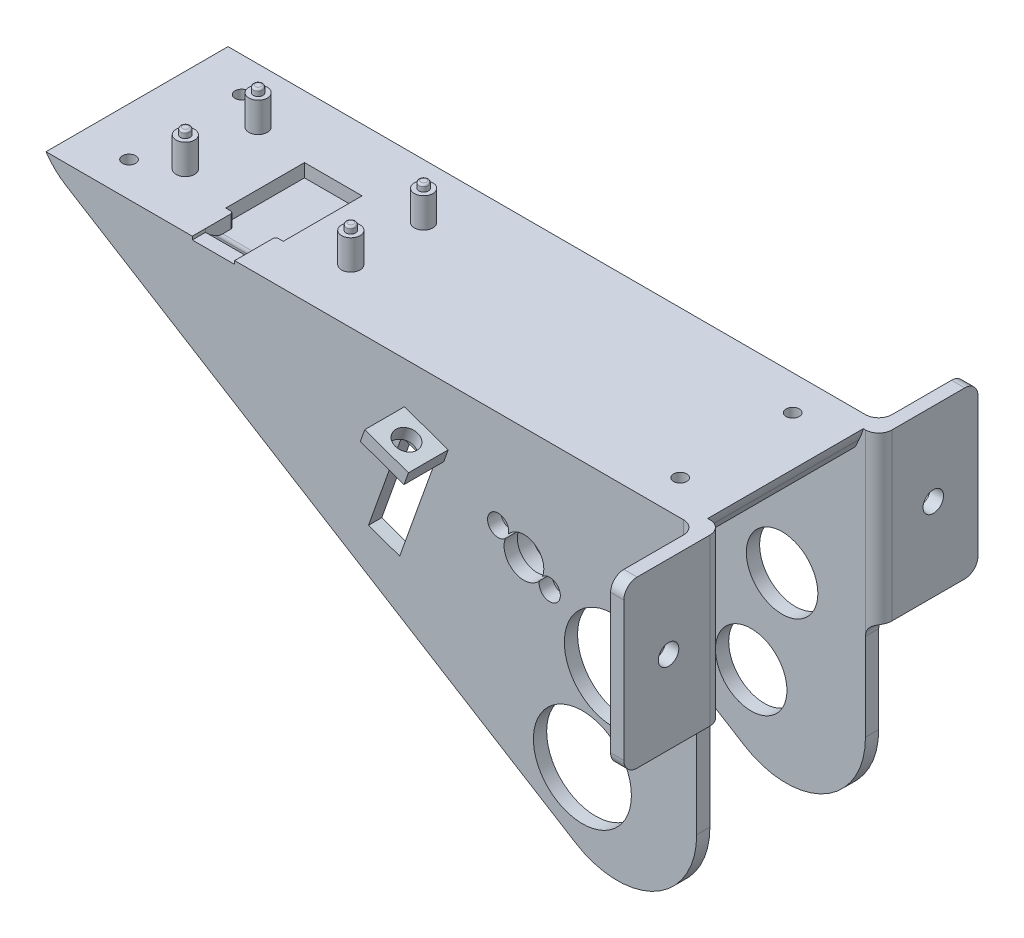
SolidWorks part; units mm, degrees
material "尼龙 101"
ref_plane "前视基准面" through (0, 0, 0) normal (0, 0, 1) x (1, 0, 0)
ref_plane "上视基准面" through (0, 0, 0) normal (0, 1, 0) x (1, 0, 0)
ref_plane "右视基准面" through (0, 0, 0) normal (1, 0, 0) x (0, 0, -1)
other "Configuration Table"
sketch "草图1" plane through (0, 0, 0) normal (0, 1, 0) x (1, 0, 0)
  line L1 (-50, 12.75) -> (50, 12.75)
  line L2 (-50, 12.75) -> (-50, -12.75)
  line L3 (-50, -12.75) -> (50, -12.75)
  line L4 (50, 12.75) -> (50, -12.75)
  line L5 (-50, 12.75) -> (50, -12.75) construction
  line L6 (-50, -12.75) -> (50, 12.75) construction
  point P0 (0, 0)
  dimension "D1" = 100
  dimension "D2" = 25.5
extrude "凸台-拉伸1" add sketch "草图1" along normal blind 3
sketch "草图2" plane through (0, 3, 0) normal (0, 1, 0) x (1, 0, 0)
  line L0 (0, 0) -> (0, 5.35) construction
  line L1 (-5.35, 5.35) -> (5.35, 5.35)
  line L2 (5.35, 5.35) -> (5.35, -7.55)
  line L3 (5.35, -7.55) -> (4.35, -7.55)
  line L4 (4.35, -7.55) -> (4.35, 4.35)
  line L5 (4.35, 4.35) -> (-4.35, 4.35)
  line L6 (-4.35, -7.55) -> (-4.35, 4.35)
  line L7 (-5.35, -7.55) -> (-4.35, -7.55)
  line L8 (-5.35, 5.35) -> (-5.35, -7.55)
  point P9 (0, 4.35)
  dimension "D1" = 8.7
  dimension "D2" = 11.9
  dimension "D3" = 4.35
  dimension "D4" = 1
  dimension "D5" = 1
extrude "凸台-拉伸2" add sketch "草图2" along normal blind 1.5
sketch "草图5" plane through (0, 3, 0) normal (0, 1, 0) x (1, 0, 0)
  circle A0 centre (-10.5, 5.5) radius 1.4
  circle A1 centre (-10.5, -5.5) radius 1.4
  circle A2 centre (-35.5, -5.5) radius 1.4
  circle A3 centre (-35.5, 5.5) radius 1.4
  dimension "D1" = 2.8
  dimension "D2" = 25
  dimension "D3" = 11
extrude "凸台-拉伸3" add sketch "草图5" along normal blind 4.5
sketch "草图6" plane through (0, 7.5, 0) normal (0, 1, 0) x (1, 0, 0)
  circle A0 centre (-35.5, -5.5) radius 0.725
  circle A1 centre (-35.5, 5.5) radius 0.725
  circle A2 centre (-10.5, 5.5) radius 0.725
  circle A3 centre (-10.5, -5.5) radius 0.725
  dimension "D1" = 1.45
extrude "凸台-拉伸4" add sketch "草图6" along normal blind 1
sketch "草图7" plane through (0, 3, 0) normal (0, 1, 0) x (1, 0, 0)
  line L0 (0, 0) -> (0, 12.75) construction
  line L1 (50, 12.75) -> (-50, 12.75) construction
  line L2 (0, 0) -> (50, 0) construction
  line L3 (50, -12.75) -> (50, 12.75) construction
  circle A0 centre (42.25, 8.5) radius 1
  circle A1 centre (-41, 8.5) radius 1
  circle A2 centre (-41, -8.5) radius 1
  circle A3 centre (42.25, -8.5) radius 1
  dimension "D1" = 83.25
extrude "切除-拉伸1" cut sketch "草图7" against normal blind 10
sketch "草图8" plane through (0, 0, 0) normal (0, -1, 0) x (1, 0, 0)
  circle A0 centre (-41, 8.5) radius 2
  circle A1 centre (42.25, 8.5) radius 2
  circle A2 centre (42.25, -8.5) radius 2
  circle A3 centre (-41, -8.5) radius 2
  dimension "D1" = 4
extrude "切除-拉伸2" cut sketch "草图8" against normal blind 1
fillet "圆角1" radius 2 4 edges at (-50, 1.5, -12.75) (50, 1.5, -12.75) (-50, 1.5, 12.75) (50, 1.5, 12.75)
fillet "圆角2" radius 0.3 4 edges at (-10.5, 8.5, -4.775) (-10.5, 8.5, 6.225) (-35.5, 8.5, 6.225) (-35.5, 8.5, -4.775)
sketch "草图15" plane through (0, 3, 0) normal (0, 1, 0) x (1, 0, 0)
  line L0 (-23, 0) -> (-23, 12.75) construction
  line L2 (-27.35, 4.35) -> (-18.65, 4.35)
  line L3 (-18.65, 4.35) -> (-18.65, -7.55)
  line L4 (-18.65, -7.55) -> (-19.8, -7.55)
  line L5 (-19.8, -7.55) -> (-19.8, -12.75)
  line L7 (-19.8, -12.75) -> (-26.2, -12.75)
  line L8 (-26.2, -7.55) -> (-26.2, -12.75)
  line L9 (-27.35, -7.55) -> (-26.2, -7.55)
  line L10 (-27.35, 4.35) -> (-27.35, -7.55)
  line L12 (42.25, 8.5) -> (-23, 8.5) construction
  point P14 (-23, -12.75)
  point P17 (-23, 4.35)
  dimension "D1" = 6.4
extrude "切除-拉伸8" cut sketch "草图15" against normal blind 2
sketch "草图17" plane through (0, 4.5, 0) normal (0, 1, 0) x (1, 0, 0)
  line L8 (-4.35, -7.55) -> (-4.35, 4.35)
  line L9 (-4.35, 4.35) -> (4.35, 4.35)
  line L10 (4.35, 4.35) -> (4.35, -7.55)
  line L11 (4.35, -7.55) -> (5.35, -7.55)
  line L12 (5.35, -7.55) -> (5.35, 5.35)
  line L13 (5.35, 5.35) -> (-5.35, 5.35)
  line L14 (-5.35, 5.35) -> (-5.35, -7.55)
  line L15 (-5.35, -7.55) -> (-4.35, -7.55)
  line L16 (-4.35, -7.55) -> (-4.35, 4.35)
  line L17 (-4.35, 4.35) -> (4.35, 4.35)
  line L18 (4.35, 4.35) -> (4.35, -7.55)
  line L19 (4.35, -7.55) -> (5.35, -7.55)
  line L20 (5.35, -7.55) -> (5.35, 5.35)
  line L21 (5.35, 5.35) -> (-5.35, 5.35)
  line L22 (-5.35, 5.35) -> (-5.35, -7.55)
  line L23 (-5.35, -7.55) -> (-4.35, -7.55)
  dimension "D1" = 0
extrude "切除-拉伸9" cut sketch "草图17" against normal blind 1.5
sketch "草图18" plane through (-19.8, 0, 0) normal (-1, 0, 0) x (0, 0, 1)
  line L0 (12.75, 1) -> (9.75, 1)
  line L2 (12.75, 1) -> (12.75, 3) construction
  line L3 (12.75, 2.6) -> (12.75, 1)
  line L5 (12.75, 3) -> (12.75, 0) construction
  line L6 (12.75, 2.6) -> (12.25, 2.6)
  line L7 (12.25, 2.6) -> (9.75, 1)
  line L8 (12.75, 3) -> (10.75, 3) construction
  dimension "D1" = 3
  dimension "D2" = 0.4
  dimension "D3" = 0.5
extrude "凸台-拉伸6" add sketch "草图18" along normal up to surface (6.4 mm away) up to face at (-26.2, 2, 10.15)
fillet "圆角3" radius 2 1 edges at (-23, 1, 9.75)
fillet "圆角5" radius 1 1 edges at (-23, 2.6, 12.25)
fillet "圆角6" radius 0.4 2 edges at (-19.8, 2, 7.55) (-26.2, 2, 7.55)
ref_plane "基准面1" through (0, 0, 0) normal (0, 0, -1) x (-1, 0, 0)
sketch "草图26" plane through (0, 0, -12.75) normal (0, 0, -1) x (-1, 0, 0)
  line L0 (50, 3) -> (-47.2265, -57.0098)
  line L1 (-50, 3) -> (-50, -58.7217)
  line L3 (-47.2265, -57.0098) -> (-50, -58.7217)
  line L4 (-50, 3) -> (50, 3)
  line L6 (-51, 3) -> (49.4801, 3) construction
  line L7 (-48, 3) -> (-50, 3) construction
extrude "凸台-拉伸12" add sketch "草图26" against normal mid plane 2
ref_plane "基准面2" through (0, 0, -11.75) normal (0, 0, -1) x (-1, 0, 0)
ref_plane "基准面3" through (0, 0, 0) normal (0, 0, 1) x (1, 0, 0)
mirror "镜向1" about plane through (0, 0, 0) normal (0, 0, 1) of "凸台-拉伸12"
sketch "草图34" plane through (0, 0, -13.75) normal (0, 0, -1) x (-1, 0, 0)
  line L0 (50, 15.0087) -> (50, 8.5792)
  line L1 (50, 8.5792) -> (50, 13) construction
  line L2 (45.2523, 0.0696) -> (38.3449, -4.1938)
  line L3 (-50, -58.7217) -> (50, 3) construction
  line L4 (50, 15.0087) -> (52.8395, -4.7654)
  line L5 (52.8395, -4.7654) -> (38.3449, -4.1938)
  arc A0 (45.2523, 0.0696) -> (50, 8.5792) centre (40, 8.5792) ccw
  point P12 (50, 3)
  dimension "D1" = 10
extrude "切除-拉伸20" cut sketch "草图34" against normal up to surface (27.5 mm away) up to face at (16.6667, -17.5739, 13.75)
sketch "草图35" plane through (0, 0, -11.75) normal (0, 0, 1) x (1, 0, 0)
  line L9 (50, 10.631) -> (50, 5.5397)
  line L10 (57.0725, -23.7563) -> (50, 10.631)
  line L11 (33.7407, -30.9984) -> (57.0725, -23.7563)
  line L12 (49.0355, 1.255) -> (33.7407, -30.9984)
  arc A2 (49.0355, 1.255) -> (50, 5.5397) centre (40, 5.5397) ccw
extrude "切除-拉伸21" cut sketch "草图35" along normal up to surface (23.5 mm away) up to face at (30.8649, -10.5443, 11.75)
sketch "草图37" plane through (0, 0, -13.75) normal (0, 0, -1) x (-1, 0, 0)
  line L0 (-50, -58.7217) -> (-31.6973, -47.425)
  line L1 (-50, 3) -> (-50, -58.7217) construction
  line L2 (-50, -58.7217) -> (-50, -37.2134)
  line L3 (-50, -58.7217) -> (45.2523, 0.0696) construction
  arc A0 (-50, -37.2134) -> (-31.6973, -47.425) centre (-38, -37.2134) ccw
  dimension "D1" = 12
  dimension "D2" = 12
extrude "切除-拉伸22" cut sketch "草图37" against normal blind 30
sketch "草图41" plane through (0, 0, 13.75) normal (0, 0, 1) x (1, 0, 0)
  circle A0 centre (23.9052, -13.9776) radius 3
extrude "切除-拉伸25" cut sketch "草图41" against normal blind 50
sketch "草图48" plane through (0, 0, 13.75) normal (0, 0, 1) x (1, 0, 0)
  line L4 (-19.8024, 3) -> (-26.1988, 3)
  line L6 (-19.8024, 2.5) -> (-26.1988, 2.5)
  line L8 (-26.1988, 3) -> (-26.1988, 2.5)
  line L9 (-19.8024, 2.5) -> (-19.8024, 3)
extrude "切除-拉伸30" cut sketch "草图48" against normal blind 5
sketch "草图50" plane through (50, 0, 0) normal (1, 0, 0) x (0, 0, -1)
  line L0 (0, 0) -> (0, -12.9975) construction
  line L1 (11.75, 3) -> (26.75, 3)
  line L2 (11.75, 3) -> (11.75, -22)
  line L3 (11.75, -22) -> (26.75, -22)
  line L4 (26.75, 3) -> (26.75, -22)
  line L5 (-26.75, 3) -> (-26.75, -22)
  line L6 (-11.75, -22) -> (-26.75, -22)
  line L7 (-11.75, 3) -> (-11.75, -22)
  line L8 (-11.75, 3) -> (-26.75, 3)
  circle A0 centre (-20, -9.5) radius 1.55
  circle A1 centre (20, -9.5) radius 1.55
  point P8 (20, -9.5)
  point P14 (-20, -9.5)
  dimension "D1" = 12.5
  dimension "D2" = 40
extrude "凸台-拉伸14" add sketch "草图50" along normal blind 2
fillet "圆角8" radius 2 6 edges at (51, 3, -26.75) (51, -22, -26.75) (51, -22, 26.75) (51, 3, 26.75) (50, -9.5, 13.75) (50, -9.5, -13.75)
fillet "圆角9" radius 2 2 edges at (50, -22, 12.75) (50, -22, -12.75)
fillet "圆角10" radius 2 2 edges at (52, -9.5, -11.75) (52, -9.5, 11.75)
sketch "草图51" plane through (0, 0, 13.75) normal (0, 0, 1) x (1, 0, 0)
  line L0 (23.9052, -13.9776) -> (17.8526, -10.4832) construction
  line L1 (23.9052, -13.9776) -> (19.6123, -21.4131) construction
  circle A0 centre (20.008, -11.7276) radius 0.8
  circle A1 centre (27.8023, -16.2276) radius 0.8
  dimension "D1" = 9
  dimension "D2" = 1.6
sketch "草图52" plane through (0, 0, 11.75) normal (0, 0, -1) x (-1, 0, 0)
  line L1 (-21.026, -5.9645) -> (-32.2843, -12.4645)
  line L2 (-21.026, -5.9645) -> (-15.526, -15.4908)
  line L3 (-15.526, -15.4908) -> (-26.7843, -21.9908)
  line L4 (-32.2843, -12.4645) -> (-26.7843, -21.9908)
  line L5 (-21.026, -5.9645) -> (-26.7843, -21.9908) construction
  line L6 (-15.526, -15.4908) -> (-32.2843, -12.4645) construction
  circle A0 centre (-23.9052, -13.9776) radius 3.5
  point P0 (-23.9052, -13.9776)
  dimension "D1" = 13
  dimension "D2" = 11
extrude "凸台-拉伸15" add sketch "草图52" along normal blind 2.5
extrude "切除-拉伸31" cut sketch "草图51" against normal up to surface (4.5 mm away) up to face at (23.9052, -13.9776, 9.25)
sketch "草图53" plane through (0, 0, 13.75) normal (0, 0, 1) x (1, 0, 0)
  line L0 (23.9052, -13.9776) -> (25.4052, -13.9776) construction
  circle A0 centre (20.008, -11.7276) radius 1.6
  circle A2 centre (27.8023, -16.2276) radius 1.6
  point P8 (27.8023, -16.2276)
extrude "切除-拉伸34" cut sketch "草图53" against normal blind 2
fillet "圆角11" radius 1 4 edges at (29.5343, -17.2276, 11.75) (21.1552, -18.7408, 11.75) (18.276, -10.7276, 11.75) (26.6552, -9.2145, 11.75)
sketch "草图54" plane through (0, 0, -13.75) normal (0, 0, -1) x (-1, 0, 0)
  circle A0 centre (-23.9052, -13.9776) radius 6.5
extrude "切除-拉伸35" cut sketch "草图54" against normal up to surface (2 mm away) up to face at (26.9052, -13.9776, -11.75)
sketch "草图55" plane through (0, 0, -13.75) normal (0, 0, -1) x (-1, 0, 0)
  line L1 (-21.026, -5.9645) -> (-15.526, -15.4908)
  line L2 (-21.026, -5.9645) -> (-32.2843, -12.4645)
  line L3 (-32.2843, -12.4645) -> (-26.7843, -21.9908)
  line L4 (-15.526, -15.4908) -> (-26.7843, -21.9908)
  line L5 (-21.026, -5.9645) -> (-26.7843, -21.9908) construction
  line L6 (-32.2843, -12.4645) -> (-15.526, -15.4908) construction
  point P0 (-23.9052, -13.9776)
extrude "切除-拉伸36" cut sketch "草图55" against normal up to next (2 mm away)
sketch "草图57" plane through (0, 0, 13.75) normal (0, 0, 1) x (1, 0, 0)
  circle A0 centre (23.9052, -13.9776) radius 15.71 construction
  circle A1 centre (37.4052, -22.0122) radius 7.4
  circle A2 centre (37.4052, -22.0122) radius 15.71 construction
  circle A4 centre (32.7357, -37.0122) radius 7.4
  dimension "D1" = 31.42
  dimension "D2" = 14.8
  dimension "D3" = 31.42
  dimension "D4" = 13.5
  dimension "D5" = 14.8
  dimension "D6" = 15
extrude "切除-拉伸37" cut sketch "草图57" against normal up to surface (2 mm away) up to face at (-23.0003, 2.695, 11.75)
sketch "草图58" plane through (0, 0, 13.75) normal (0, 0, 1) x (1, 0, 0)
  line L0 (-45.2523, 0.0696) -> (2.1042, -16.8066) construction
  line L1 (6.8141, -18.485) -> (10.171, -9.0653)
  line L2 (10.171, -9.0653) -> (5.4611, -7.3869)
  line L3 (5.4611, -7.3869) -> (2.1042, -16.8066)
  line L5 (6.8141, -18.485) -> (5.1357, -23.1949)
  line L6 (5.1357, -23.1949) -> (0.4258, -21.5165)
  line L7 (2.1042, -16.8066) -> (0.4258, -21.5165)
  line L8 (6.8141, -18.485) -> (37.476, -29.4119) construction
  circle A0 centre (37.4052, -22.0122) radius 7.4 construction
  dimension "D1" = 30
  dimension "D2" = 10
  dimension "D3" = 5
  dimension "D4" = 5
  dimension "D5" = 5
extrude "切除-拉伸38" cut sketch "草图58" against normal up to surface (27.5 mm away)
sketch "草图59" plane through (0, 0, 13.75) normal (0, 0, 1) x (1, 0, 0)
  line L0 (5.1905, -5.1672) -> (11.7843, -7.517)
  line L1 (10.171, -9.0653) -> (5.4611, -7.3869) construction
  line L2 (5.1905, -5.1672) -> (5.8619, -3.2833)
  line L3 (5.8619, -3.2833) -> (12.4557, -5.6331)
  line L4 (12.4557, -5.6331) -> (11.7843, -7.517)
  line L5 (5.4611, -7.3869) -> (0.4258, -21.5165) construction
  dimension "D1" = 7
  dimension "D2" = 2
  dimension "D3" = 2
  dimension "D4" = 1
extrude "凸台-拉伸16" add sketch "草图59" along normal blind 6
sketch "草图61" plane through (-0.3777, -1.0597, 0) normal (0.3357, 0.942, 0) x (0.942, -0.3357, 0)
  line L0 (10.1239, -13.75) -> (10.1239, -19.75) construction
  line L1 (13.6239, -13.75) -> (6.6239, -13.75) construction
  line L2 (13.6239, -19.75) -> (6.6239, -19.75) construction
  circle A0 centre (10.1239, -16.75) radius 1.7
extrude "切除-拉伸39" cut sketch "草图61" against normal blind 6
sketch "草图62" plane through (0, 0, -13.75) normal (0, 0, -1) x (-1, 0, 0)
  circle A0 centre (-32.7357, -37.0122) radius 7.4 construction
  circle A1 centre (-37.4052, -22.0122) radius 7.4 construction
  circle A2 centre (-32.7357, -37.0122) radius 7.4
  circle A3 centre (-37.4052, -22.0122) radius 7.4
  circle A4 centre (-37.4052, -22.0122) radius 5.4
  circle A5 centre (-32.7357, -37.0122) radius 5.4
  dimension "D1" = 2
  dimension "D2" = 2
extrude "切除-拉伸40" cut sketch "草图62" against normal up to surface (2 mm away) contours A4 | A5 up to face at (5.2984, -15.2909, -11.75)
mirror "镜向2" about plane through (0, 0, 0) normal (0, 0, 1) of "切除-拉伸39", "凸台-拉伸16"
